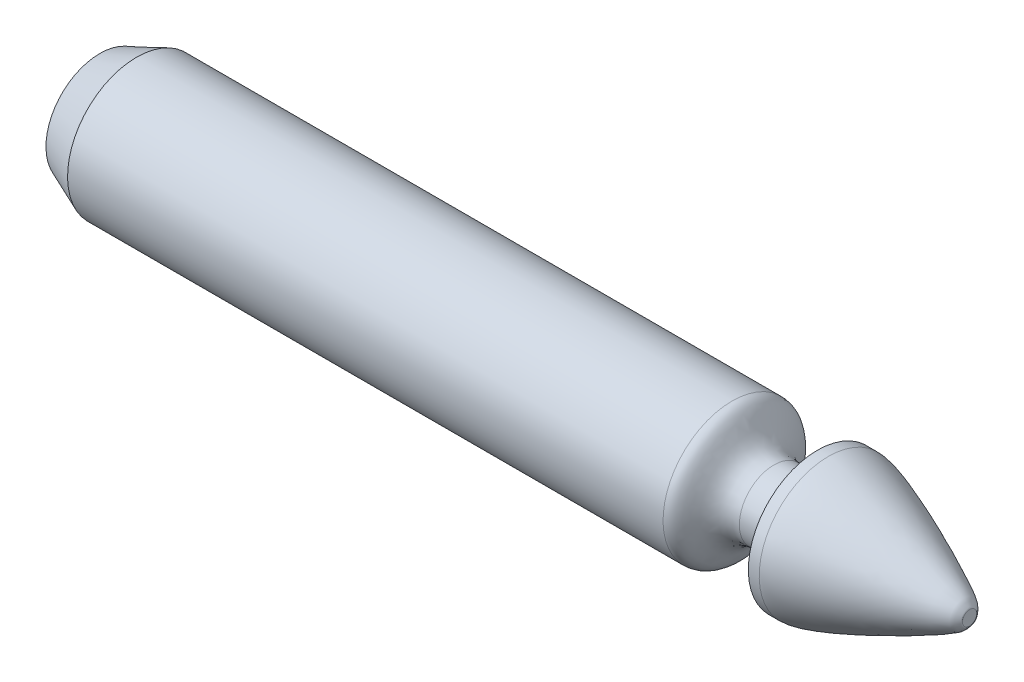
SolidWorks part; units mm, degrees
material "Stainless Steel (ferritic)"
ref_plane "Front" through (0, 0, 0) normal (0, 0, 1) x (1, 0, 0)
ref_plane "Top" through (0, 0, 0) normal (0, 1, 0) x (1, 0, 0)
ref_plane "Right" through (0, 0, 0) normal (1, 0, 0) x (0, 0, -1)
sketch "body_sketch" plane through (0, 0, 0) normal (0, 0, 1) x (1, 0, 0)
  line L1 (-16.7357, 3.175) -> (-10.9218, 3.175)
  line L2 (-38.31, 3.175) -> (-20.8111, 3.175)
  line L3 (-19.1074, 3.175) -> (-22.5343, 3.175) construction
  line L4 (-6.5, 3.175) -> (-7, 3.175)
  line L5 (-15.6683, 3.175) -> (-17.809, 3.175) construction
  line L6 (-40, 0) -> (-40, 2.4778)
  line L7 (-40, 2.4778) -> (-38.31, 3.175)
  line L9 (-7, 3.175) -> (-7, 1.5875)
  line L10 (-7, 1.5875) -> (-9, 1.5875)
  line L13 (14.3233, 1.5875) -> (12.3233, 1.5875) construction
  line L14 (-10.9218, 3.175) -> (-7, 3.175) construction
  line L15 (0, 0) -> (-40, 0)
  line L17 (0, 0.3278) -> (0, 0)
  spline S0 degree 3 poles (-6.5, 3.175) (-5.4841, 3.175) (-0.4543, 0.8964) (-0.0546, 0.4243) (0, 0.3773) (0, 0.3278) knots 0 0 0 0 0.586138 0.686138 1 1 1 1
  spline S1 degree 3 poles (-10.9218, 3.175) (-10.1654, 3.175) (-10.25, 1.5875) (-9, 1.5875) knots 0 0 0 0 1 1 1 1
  spline S2 degree 3 poles (-20.8111, 3.175) (-19.3832, 3.175) (-18.0736, 3.175) (-16.7357, 3.175) knots 0 0 0 0 1 1 1 1
  dimension "D1" = 3.175
  dimension "D2" = 0.5
  dimension "D3" = 2
  dimension "D4" = 1.5875
  dimension "D5" = 40
  dimension "D6" = 7
  dimension "D7" = 3.175
revolve "body" add sketch "body_sketch" angle 360 about L15
sketch "minimum_diameter" plane through (0, 0, 0) normal (1, 0, 0) x (0, 0, -1)
  circle A0 centre (0, 0) radius 1.5875 construction
  circle A2 centre (0, 0) radius 1.5875 construction
